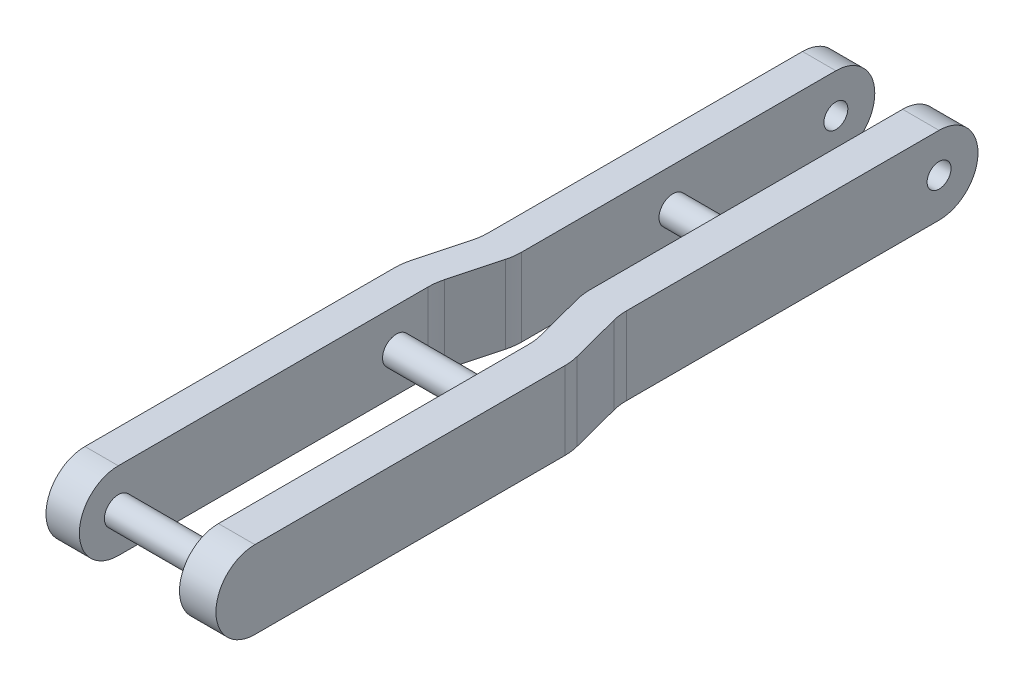
SolidWorks part; units mm, degrees
ref_plane "前视基准面" through (0, 0, 0) normal (0, 0, 1) x (1, 0, 0)
ref_plane "上视基准面" through (0, 0, 0) normal (0, 1, 0) x (1, 0, 0)
ref_plane "右视基准面" through (0, 0, 0) normal (1, 0, 0) x (0, 0, -1)
sketch "草图1" plane through (0, 0, 0) normal (0, 1, 0) x (1, 0, 0)
  line L0 (-5, 0) -> (5, 0) construction
  line L1 (5, 0) -> (5, 62.718)
  line L2 (4.6766, 65.2405) -> (2.3234, 74.2681)
  line L3 (2, 76.7906) -> (2, 140)
  line L4 (5, 0) -> (-1.5534, 0)
  line L5 (-1.5534, 0) -> (-1.5534, 62.718)
  line L6 (-1.8768, 65.2405) -> (-4.2301, 74.2681)
  line L7 (-4.5534, 76.7906) -> (-4.5534, 140)
  line L8 (-4.5534, 140) -> (2, 140)
  arc A0 (-4.2301, 74.2681) -> (-4.5534, 76.7906) centre (5.4466, 76.7906) cw
  arc A1 (2.3234, 74.2681) -> (2, 76.7906) centre (12, 76.7906) cw
  arc A2 (5, 62.718) -> (4.6766, 65.2405) centre (-5, 62.718) ccw
  arc A3 (-1.5534, 62.718) -> (-1.8768, 65.2405) centre (-11.5534, 62.718) ccw
  point P4 (0, 0)
  point P14 (-4.5534, 75.5086)
  point P17 (2, 75.5086)
  point P20 (5, 64)
  point P23 (-1.5534, 64)
  dimension "D8" = 10
  dimension "D9" = 10
  dimension "D10" = 10
  dimension "D11" = 10
  dimension "D1" = 10
  dimension "D2" = 64
  dimension "D3" = 140
  dimension "D4" = 3
  dimension "D5" = 6.5534
  dimension "D6" = 64
  dimension "D7" = 3
extrude "凸台-拉伸2" add sketch "草图1" along normal blind 14
fillet "圆角1" 2 edges at (1.7233, 14, 0) (1.7233, 0, 0) type full round first side face at (0.2233, 14, -69.8362) second side face at (0.2233, 0, -69.8362) middle face at (1.7233, 7, 0)
fillet "圆角2" 2 edges at (-1.2767, 14, -140) (-1.2767, 0, -140) type full round first side face at (0.2233, 14, -71.0029) second side face at (0.2233, 0, -71.0029) middle face at (-1.2767, 7, -140)
sketch "草图2" plane through (2, 0, 0) normal (1, 0, 0) x (0, 0, -1)
  circle A0 centre (133, 7) radius 2.15
  dimension "D1" = 4.3
extrude "切除-拉伸1" cut sketch "草图2" against normal up to next
sketch "草图4" plane through (0, 0, 0) normal (0, 1, 0) x (1, 0, 0)
  line L0 (0, 0) -> (-67.1091, 0) construction
  line L1 (-19.5534, 0) -> (-25.5534, 0)
  line L2 (-25.5534, 0) -> (-25.5534, 62.6839)
  line L3 (-25.2129, 65.2713) -> (-22.894, 73.9283)
  line L4 (-22.5534, 76.5157) -> (-22.5534, 140)
  line L5 (-22.5534, 140) -> (-16.5534, 140)
  line L6 (-16.5534, 140) -> (-16.5534, 76.5157)
  line L7 (-16.894, 73.9283) -> (-19.2129, 65.2713)
  line L8 (-19.5534, 62.6839) -> (-19.5534, 0)
  line L10 (-4.5534, 133) -> (-4.5534, 76.7906) construction
  arc A1 (-19.2129, 65.2713) -> (-19.5534, 62.6839) centre (-9.5534, 62.6839) ccw
  arc A2 (-25.5534, 62.6839) -> (-25.2129, 65.2713) centre (-15.5534, 62.6839) cw
  arc A3 (-16.5534, 76.5157) -> (-16.894, 73.9283) centre (-26.5534, 76.5157) cw
  arc A4 (-22.894, 73.9283) -> (-22.5534, 76.5157) centre (-32.5534, 76.5157) ccw
  point P16 (-19.5534, 64)
  point P19 (-25.5534, 64)
  point P22 (-16.5534, 75.1996)
  dimension "D8" = 10
  dimension "D1" = 6
  dimension "D2" = 64
  dimension "D3" = 64
  dimension "D4" = 140
  dimension "D5" = 6
  dimension "D6" = 3
  dimension "D7" = 12
extrude "凸台-拉伸3" add sketch "草图4" along normal blind 14 separate body
fillet "圆角3" 2 edges at (-19.5534, 14, -140) (-19.5534, 0, -140) type full round first side face at (-21.0534, 14, -69.7332) second side face at (-21.0534, 0, -69.7332) middle face at (-19.5534, 7, -140)
fillet "圆角4" 2 edges at (-22.5534, 0, 0) (-22.5534, 14, 0) type full round first side face at (-21.0534, 0, -68.5665) second side face at (-21.0534, 14, -68.5665) middle face at (-22.5534, 7, 0)
sketch "草图8" plane through (-19.5534, 0, 0) normal (1, 0, 0) x (0, 0, -1)
  circle A0 centre (7, 7) radius 2.5
  circle A1 centre (57, 7) radius 2.5
  dimension "D1" = 5
  dimension "D2" = 5
  dimension "D3" = 50
extrude "凸台-拉伸5" add sketch "草图8" along normal up to next
sketch "草图10" plane through (-22.5534, 0, 0) normal (-1, 0, 0) x (0, 0, 1)
  circle A0 centre (-133, 7) radius 2.15
  dimension "D1" = 4.3
extrude "切除-拉伸5" cut sketch "草图10" against normal up to next
sketch "草图11" plane through (-16.5534, 0, 0) normal (1, 0, 0) x (0, 0, -1)
  circle A0 centre (103.7, 7) radius 2.5
  dimension "D2" = 5
extrude "凸台-拉伸6" add sketch "草图11" along normal up to next
